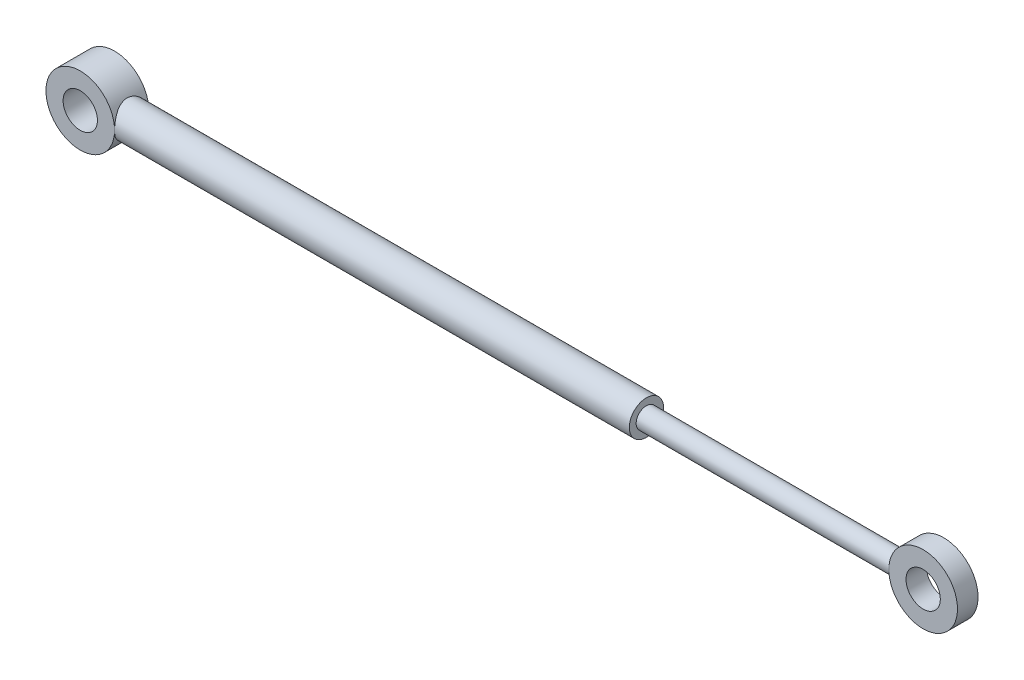
SolidWorks part; units mm, degrees
ref_plane "前视基准面" through (0, 0, 0) normal (0, 0, 1) x (1, 0, 0)
ref_plane "上视基准面" through (0, 0, 0) normal (0, 1, 0) x (1, 0, 0)
ref_plane "右视基准面" through (0, 0, 0) normal (1, 0, 0) x (0, 0, -1)
sketch "草图1" plane through (0, 0, 0) normal (0, 0, 1) x (1, 0, 0)
  circle A0 centre (0, 0) radius 5
extrude "拉伸-薄壁1" add sketch "草图1" along normal blind 10 thin thin type one direction wall 5
sketch "草图2" plane through (0, 0, 0) normal (1, 0, 0) x (0, 0, -1)
  circle A0 centre (-5, 0) radius 3
extrude "凸台-拉伸1" add sketch "草图2" along normal blind 230 from offset 7
sketch "草图3" plane through (0, 0, 0) normal (0, 0, 1) x (1, 0, 0)
  circle A0 centre (243.6437, 0) radius 5
extrude "拉伸-薄壁2" add sketch "草图3" along normal blind 10 separate body thin thin type one direction wall 5
sketch "草图5" plane through (0, 0, 0) normal (0, 1, 0) x (1, 0, 0)
  line L0 (237, -2) -> (10, -2) construction
  line L1 (233.2319, -2) -> (258.8447, -2)
  line L2 (233.2319, -2) -> (233.2319, 3.2738)
  line L3 (233.2319, 3.2738) -> (258.8447, 3.2738)
  line L4 (258.8447, -2) -> (258.8447, 3.2738)
  line L5 (10, -8) -> (237, -8) construction
  line L6 (233.2319, -8) -> (259.7486, -8)
  line L7 (233.2319, -8) -> (233.2319, -13.2991)
  line L8 (233.2319, -13.2991) -> (259.7486, -13.2991)
  line L9 (259.7486, -8) -> (259.7486, -13.2991)
extrude "切除-拉伸2" cut sketch "草图5" against normal blind 16 and the other way blind 16
sketch "草图6" plane through (0, 0, 0) normal (1, 0, 0) x (0, 0, -1)
  circle A0 centre (-5, 0) radius 3
extrude "拉伸-薄壁3" add sketch "草图6" along normal blind 155 from offset 5 separate body thin thin type one direction wall 2
equation "\"、\"=5"
